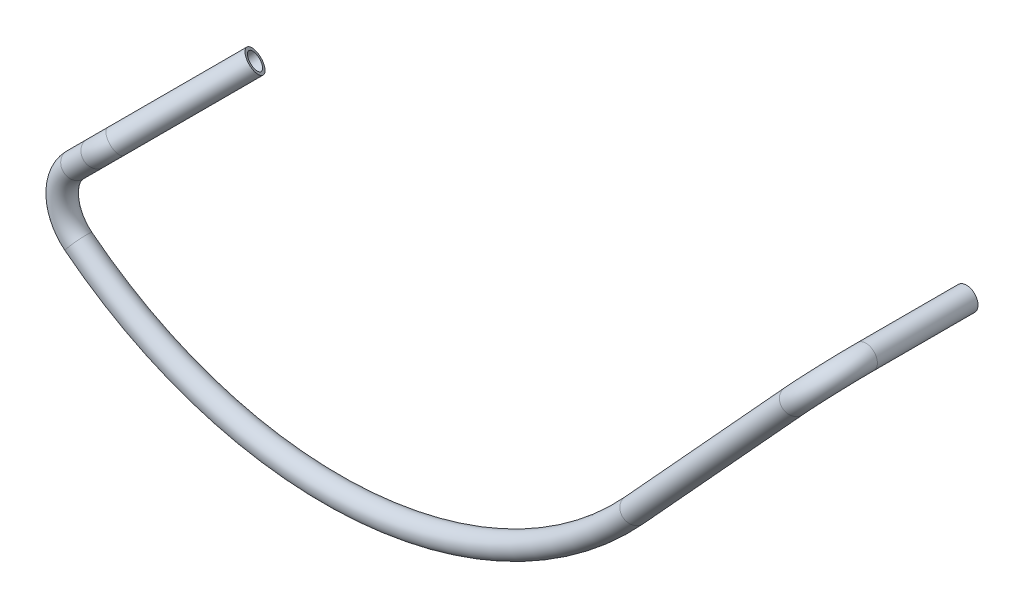
SolidWorks part; units mm, degrees
material "AISI Type 316L stainless steel"
ref_plane "Front Plane" through (0, 0, 0) normal (0, 0, 1) x (1, 0, 0)
ref_plane "Top Plane" through (0, 0, 0) normal (0, 1, 0) x (1, 0, 0)
ref_plane "Right Plane" through (0, 0, 0) normal (1, 0, 0) x (0, 0, -1)
sketch "Sketch1" plane through (0, 0, 0) normal (0, 0, 1) x (1, 0, 0)
  line L0 (0, 0) -> (34.1488, -4.9099) construction
  line L1 (0, 0) -> (-20.1525, -20.1525) construction
  line L2 (0, 33.575) -> (0, 0) construction
  line L3 (34.1488, -4.9099) -> (31.0377, -4.4625)
  line L4 (-17.906, -17.906) -> (-15.9311, -15.9311)
  circle A0 centre (0, 0) radius 34.5 construction
  circle A1 centre (0, 0) radius 28.5 construction
  arc A2 (27.6954, -6.7242) -> (-17.6417, -22.3835) centre (0, 0) cw
  arc A3 (-17.6417, -22.3835) -> (-17.906, -17.906) centre (-15.7847, -20.0273) cw
  arc A4 (31.0377, -4.4625) -> (27.6954, -6.7242) centre (30.6107, -7.432) ccw
  point P15 (28.2099, -4.056)
  dimension "D1" = 69
  dimension "D4" = 57
  dimension "D5" = 5.97
  dimension "D6" = 3
  dimension "D2" = 98.182
  dimension "D3" = 135
ref_plane "Plane1" through (0, 0, 0) normal (-0.7071, 0.7071, 0) x (-0.7071, -0.7071, 0)
sketch "Sketch2" plane through (0, 0, 0) normal (-0.7071, 0.7071, 0) x (-0.7071, -0.7071, 0)
  line L0 (22.53, 0) -> (14.3028, -4.75)
  line L1 (28.3021, 0) -> (-14.8289, 0) construction
  line L2 (22.53, 0) -> (0, 0) construction
  dimension "D1" = 30
  dimension "D2" = 9.5
sketch3d "3DSketch1"
  line L0 (-17.906, -17.906, 0) -> (-15.9311, -15.9311, 0) construction
  line L1 (-15.9311, -15.9311, 0) -> (-10.1136, -10.1136, -4.75) construction
  line L2 (-17.906, -17.906, 0) -> (-16.4995, -16.4995, 0)
  line L3 (-15.4389, -15.4389, -0.4019) -> (-10.1136, -10.1136, -4.75)
  line L4 (34.1488, -4.9099, -3) -> (34.1488, -4.9099, -10)
  line L5 (32.1227, -7.1223, 0) -> (21.0181, -19.2481, 0)
  arc A0 (-17.6417, -22.3835, 0) -> (-17.906, -17.906, 0) centre (-15.7847, -20.0273, 0) ccw construction
  arc A1 (27.6954, -6.7242, 0) -> (-17.6417, -22.3835, 0) centre (0, 0, 0) ccw construction
  arc A2 (-16.4995, -16.4995, 0) -> (-15.4389, -15.4389, -0.4019) centre (-16.4995, -16.4995, -3) ccw
  arc A3 (-17.6417, -22.3835, 0) -> (-17.906, -17.906, 0) centre (-15.7847, -20.0273, 0) ccw
  arc A4 (21.0181, -19.2481, 0) -> (-17.6417, -22.3835, 0) centre (0, 0, 0) ccw
  arc A5 (32.1227, -7.1223, 0) -> (34.1488, -4.9099, -3) centre (32.1227, -7.1223, -3) ccw
  point P5 (-15.7847, -20.0273, -3)
  point P8 (0, 0, -28.5)
  point P11 (34.1488, -4.9099, 0)
  point P12 (-15.7847, -20.0273, -3)
  point P13 (0, 0, -28.5)
  point P14 (29.9103, -5.0962, -3)
  point P21 (-17.3241, -17.3241, 0)
  point P23 (-18.6208, -14.3782, -3)
  dimension "D2" = 3
  dimension "D3" = 3
  dimension "D1" = 10
ref_plane "Plane2" through (0, 0, -10) normal (0, 0, 1) x (1, 0, 0)
sketch "Sketch3" plane through (0, 0, -10) normal (0, 0, 1) x (1, 0, 0)
  circle A0 centre (34.1488, -4.9099) radius 0.8
  circle A1 centre (34.1488, -4.9099) radius 0.6
  dimension "D1" = 1.2
  dimension "D2" = 1.6
sweep "Sweep1" add profiles "Sketch3" path "3DSketch1"
ref_axis "Axis1" through (0, 0, 1.24) along (0, 0, -1)
